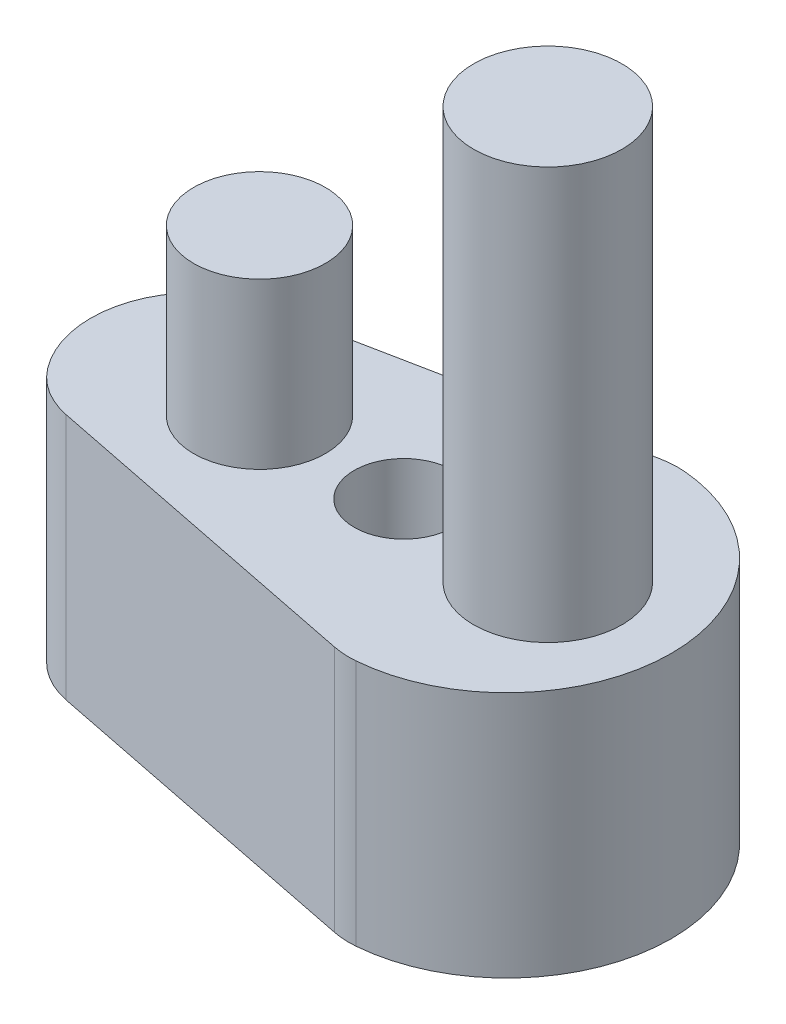
SolidWorks part; units mm, degrees
ref_plane "Front Plane" through (0, 0, 0) normal (0, 0, 1) x (1, 0, 0)
ref_plane "Top Plane" through (0, 0, 0) normal (0, 1, 0) x (1, 0, 0)
ref_plane "Right Plane" through (0, 0, 0) normal (1, 0, 0) x (0, 0, -1)
sketch "Sketch1" plane through (0, 0, 0) normal (0, 1, 0) x (1, 0, 0)
  line L0 (-0.1139, 1.9772) -> (-1.25, 1.7502)
  line L1 (-0.1139, -1.9772) -> (-1.25, -1.7502)
  line L4 (-1.25, -1.7502) -> (-4.1832, -1.1642)
  line L5 (-1.25, 1.7502) -> (-4.1832, 1.1642)
  circle A0 centre (0.5, 0) radius 0.9
  circle A1 centre (-1.25, 0) radius 0.6
  arc A2 (0.1641, 1.9933) -> (0.1641, -1.9933) centre (0, 0) cw
  arc A3 (-0.1139, -1.9772) -> (0.1641, -1.9933) centre (0.0821, -0.9966) ccw
  arc A4 (-4.7783, 0.7954) -> (-4.7783, -0.7954) centre (-3.75, 0) ccw
  arc A5 (0.1641, 1.9933) -> (-0.1139, 1.9772) centre (0.0821, 0.9966) ccw
  arc A6 (-4.1832, 1.1642) -> (-4.7783, 0.7954) centre (-3.9873, 0.1835) ccw
  arc A7 (-4.1832, -1.1642) -> (-4.7783, -0.7954) centre (-3.9873, -0.1835) cw
  circle A8 centre (-3, 0) radius 0.3
  circle A9 centre (0.5, 0) radius 0.3
  circle A10 centre (-3, 0) radius 0.8
  point P12 (-3, 0)
  point P20 (0.5, 0)
extrude "Boss-Extrude1" add sketch "Sketch1" along normal blind 3 contours A2 A5 L0 L1 A3 A9 | A0 A9 | A8 | A9 | A10 A8 region at (0.0292, 0, -1.9141) region at (-0.3745, 0, 0) region at (-3, 0, 0) region at (0.5, 0, 0) region at (-3.7774, 0, 0)
extrude "Boss-Extrude2" add sketch "Sketch1<22>" along normal blind 8 contours A0 A9 | A9 region at (-0.3745, 0, 0) region at (0.5, 0, 0)
sketch "Sketch1<22>" plane through (0, 0, 0) normal (0, 1, 0) x (1, 0, 0) same geometry as "Sketch1"
extrude "Boss-Extrude3" add sketch "Sketch1<23>" along normal blind 5 contours A10 A8 | A8 region at (-3, 0, 0) region at (-3.7774, 0, 0)
sketch "Sketch1<23>" plane through (0, 0, 0) normal (0, 1, 0) x (1, 0, 0) same geometry as "Sketch1"
